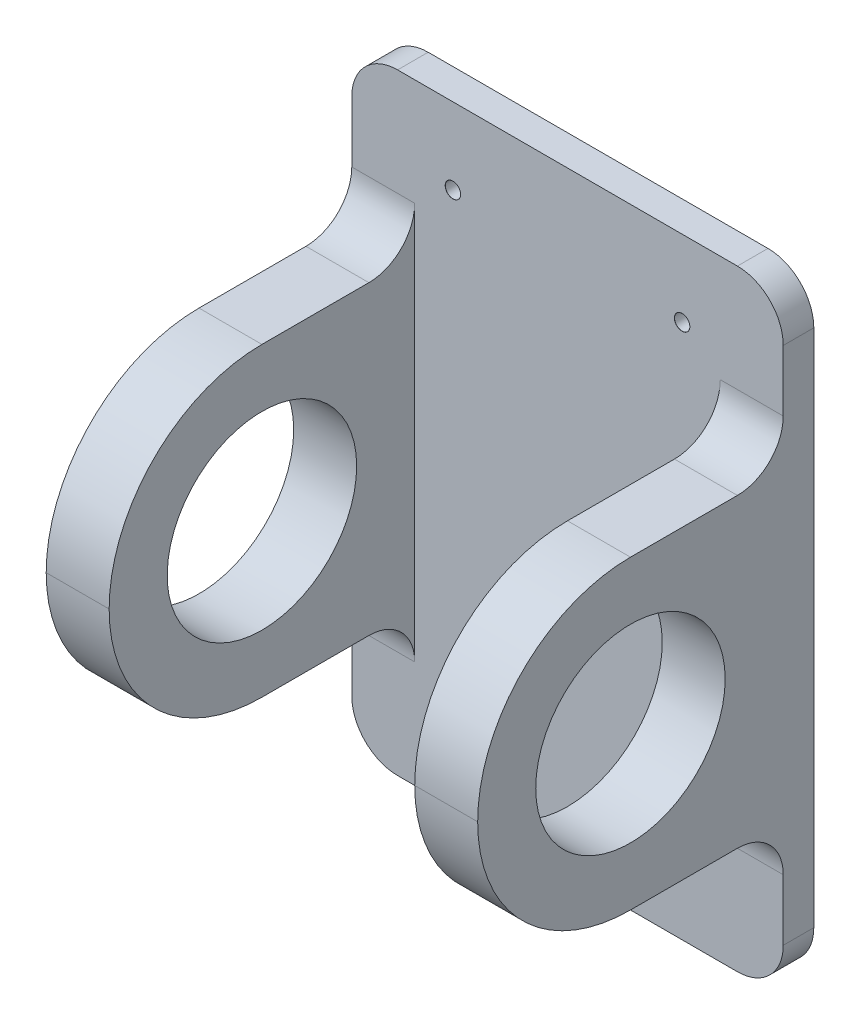
SolidWorks part; units mm, degrees
material "Rubber"
ref_plane "Front Plane" through (0, 0, 0) normal (1, 0, 0) x (0, 1, 0)
ref_plane "Top Plane" through (0, 0, 0) normal (0, 0, 1) x (0, 1, 0)
ref_plane "Right Plane" through (0, 0, 0) normal (0, 1, 0) x (-1, 0, 0)
sketch "Sketch1" plane through (0, 0, 0) normal (0, 0, 1) x (0, 1, 0)
  line L1 (-100, 70.6) -> (100, 70.6)
  line L2 (-100, 70.6) -> (-100, -70.6)
  line L3 (-100, -70.6) -> (100, -70.6)
  line L4 (100, 70.6) -> (100, -70.6)
  point P4 (0, 70.6)
  point P6 (-100, 0)
  dimension "D1" = 0
  dimension "D2" = 0
  dimension "D3" = 141.2
  dimension "D4" = 200
extrude "Boss-Extrude1" add sketch "Sketch1" against normal blind 10
sketch "Sketch2" plane through (0, 0, 0) normal (0, 0, 1) x (0, 1, 0)
  line L1 (-50, 70.6) -> (50, 70.6)
  line L2 (-50, 70.6) -> (-50, -70.6)
  line L3 (-50, -70.6) -> (50, -70.6)
  line L4 (-100, 70.6) -> (-100, -70.6)
  line L5 (-100, -70.6) -> (100, -70.6)
  line L6 (100, -70.6) -> (100, 70.6)
  line L7 (100, 70.6) -> (-100, 70.6)
  line L8 (-100, 70.6) -> (-100, -70.6)
  line L9 (-100, -70.6) -> (100, -70.6)
  line L10 (100, -70.6) -> (100, 70.6)
  line L11 (100, 70.6) -> (-100, 70.6)
  line L12 (50, 70.6) -> (50, -70.6)
  line L13 (-50, 50) -> (50, 50)
  line L14 (-50, 50) -> (-50, -50)
  line L15 (-50, -50) -> (50, -50)
  line L16 (50, 50) -> (50, -50)
  point P8 (0, 70.6)
  point P9 (0, 70.6)
  point P14 (-50, 0)
  point P15 (-50, 0)
  dimension "D2" = 0
  dimension "D3" = 100
  dimension "D4" = 0
  dimension "D5" = 100
  dimension "D1" = 0
extrude "Boss-Extrude2" add sketch "Sketch2" along normal blind 100 contours L2 L13 L12 L1 | L15 L2 L3 L12 region at (-60.3, 0, 0) region at (60.3, 0, 0)
fillet "Fillet1" radius 50 4 edges at (60.3, 50, 100) (60.3, -50, 100) (-60.3, 50, 100) (-60.3, -50, 100)
sketch "Sketch3" plane through (70.6, 0, 0) normal (1, 0, 0) x (0, 1, 0)
  line L7 (50, 0) -> (50, 50)
  line L8 (-50, 50) -> (-50, 0)
  line L9 (-50, 0) -> (-100, 0)
  line L10 (-100, 0) -> (-100, -10)
  line L11 (-100, -10) -> (100, -10)
  line L12 (100, -10) -> (100, 0)
  line L13 (100, 0) -> (50, 0)
  line L14 (50, 0) -> (50, 50)
  line L15 (-50, 50) -> (-50, 0)
  line L16 (-50, 0) -> (-100, 0)
  line L17 (-100, 0) -> (-100, -10)
  line L18 (-100, -10) -> (100, -10)
  line L19 (100, -10) -> (100, 0)
  line L20 (100, 0) -> (50, 0)
  arc A2 (50, 50) -> (0, 100) centre (0, 50) ccw
  arc A3 (0, 100) -> (-50, 50) centre (0, 50) ccw
  arc A4 (50, 50) -> (0, 100) centre (0, 50) ccw
  arc A5 (0, 100) -> (-50, 50) centre (0, 50) ccw
  point P5 (0, 50)
  dimension "D1" = 0
hole_wizard "Ø10.0mm Dowel Hole1" positions "Sketch3" profile "Sketch4" hole size "Ø10.0" standard "IS" end condition through all
sketch "Sketch4" plane through (70.6, 0, 50) normal (0, 1, 0) x (0, 0, -1)
  line L0 (0, 0) -> (0, 141.2)
  line L1 (0, 141.2) -> (31, 141.2)
  line L2 (31, 141.2) -> (31, 0)
  line L5 (31, 0) -> (0, 0)
  line L11 (0, -6.35) -> (0, 107.95) construction
  dimension "Thru Hole Dia." = 62
  dimension "Thru Hole Depth" = 141.2
sketch "Sketch5" plane through (0, 0, 0) normal (0, 0, 1) x (0, 1, 0)
  line L1 (-75, -37.5) -> (75, -37.5)
  line L2 (-75, -37.5) -> (-75, 37.5)
  line L3 (-75, 37.5) -> (75, 37.5)
  line L4 (75, -37.5) -> (75, 37.5)
  point P4 (-75, 0)
  point P6 (0, 37.5)
  point P8 (-75, 37.5)
  point P9 (-75, -37.5)
  point P10 (75, 37.5)
  point P11 (75, -37.5)
  dimension "D1" = 0
  dimension "D2" = 0
  dimension "D3" = 150
  dimension "D4" = 75
hole_wizard "Ø5.0mm Dowel Hole1" positions "Sketch5" profile "Sketch6" hole size "Ø5.0" standard "IS" end condition through all
sketch "Sketch6" plane through (37.5, 75, 0) normal (1, 0, 0) x (0, -1, 0)
  line L0 (0, 0) -> (0, 10)
  line L1 (0, 10) -> (2.5, 10)
  line L2 (2.5, 10) -> (2.5, 0.025)
  line L3 (2.5, 0.025) -> (2.525, 0)
  line L5 (2.525, 0) -> (0, 0)
  line L6 (-2.5, 0.025) -> (-2.525, 0) construction
  line L11 (0, -6.35) -> (0, 107.95) construction
  dimension "Thru Hole Dia." = 5
  dimension "Thru Hole Depth" = 10
  dimension "Near C'Sink Dia." = 5.05
  dimension "Near C'Sink Angle" = 90
fillet "Fillet2" radius 15 8 edges at (60.3, 50, 0) (-60.3, 50, 0) (60.3, -50, 0) (-60.3, -50, 0) (-70.6, -100, -5) (-70.6, 100, -5) (70.6, 100, -5) (70.6, -100, -5)
